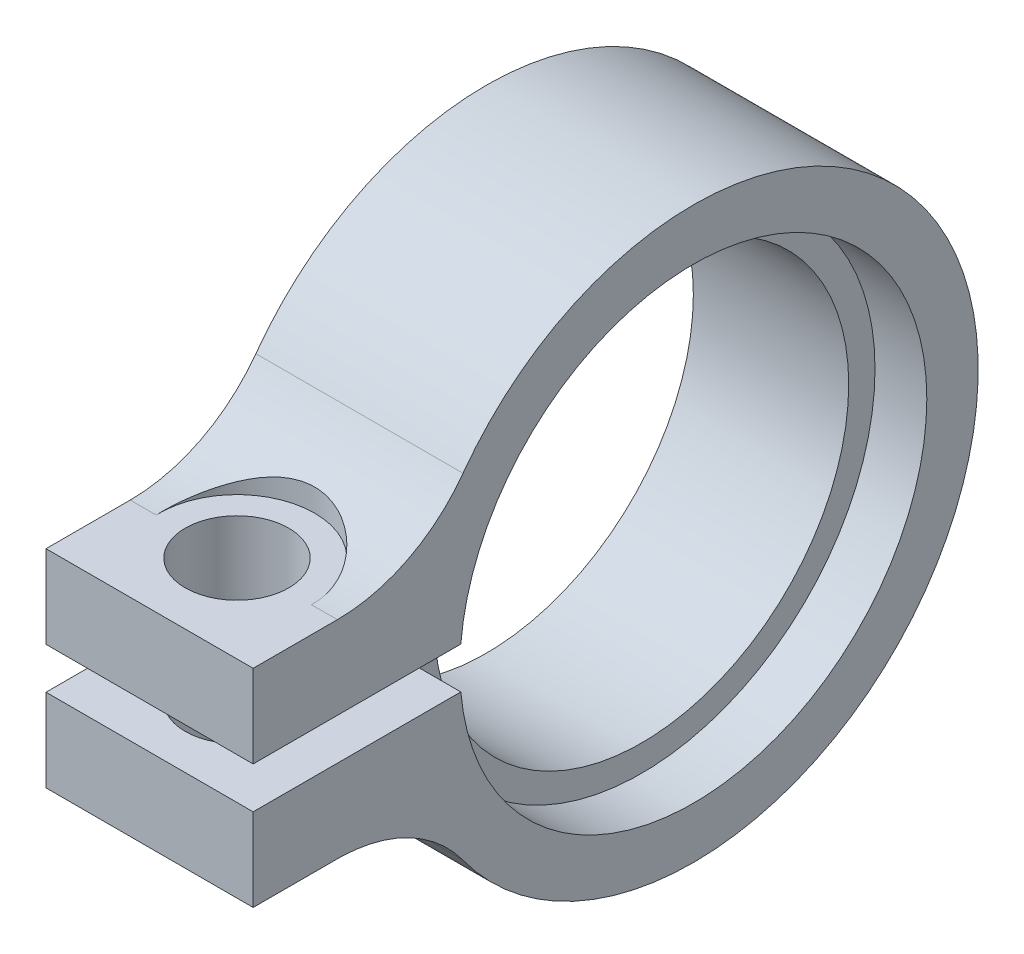
SolidWorks part; units mm, degrees
ref_plane "Front Plane" through (0, 0, 0) normal (0, 0, 1) x (1, 0, 0)
ref_plane "Top Plane" through (0, 0, 0) normal (0, 1, 0) x (1, 0, 0)
ref_plane "Right Plane" through (0, 0, 0) normal (1, 0, 0) x (0, 0, -1)
sketch "Sketch1" plane through (-50.8, 0, 0) normal (-1, 0, 0) x (0, 0, 1)
  line L0 (12.7, 187.45) -> (26.9875, 187.45) construction
  line L1 (12.6363, 186.18) -> (26.9875, 186.18)
  line L2 (12.6363, 188.72) -> (26.9875, 188.72)
  line L3 (26.9875, 188.72) -> (26.9875, 193.8)
  line L4 (26.9875, 193.8) -> (16.267, 193.8)
  line L5 (26.9875, 186.18) -> (26.9875, 181.1)
  line L6 (26.9875, 181.1) -> (16.267, 181.1)
  line L7 (12.7, 186.18) -> (26.9875, 186.18) construction
  line L8 (12.7, 188.72) -> (26.9875, 188.72) construction
  circle A0 centre (0, 187.45) radius 12.7 construction
  circle A1 centre (0, 187.45) radius 14.3129
  circle A2 centre (0, 187.45) radius 14.3129
  circle A3 centre (0, 187.45) radius 12.7
  circle A4 centre (0, 187.45) radius 17.4625
  point P18 (17.4625, 187.45)
  circle M5 centre (0, 187.45) radius 14.3129
  circle M6 centre (0, 187.45) radius 12.7
  dimension "D2" = 4.7625
  dimension "D5" = 9.525
  dimension "D6" = 5.08
  dimension "D1" = 0
  dimension "D3" = 1.27
  dimension "D4" = 1.27
extrude "Boss-Extrude1" add sketch "Sketch1" along normal blind 9.525 contours L2 L1 M6 M5 | L2 A4 L1 M5 | A4 L6 L5 L1 | A4 L2 L3 L4 region at (-50.8, 185.7756, 13.4464) region at (-50.8, 185.6864, 15.8364) region at (-50.8, 183.5916, 21.9758) region at (-50.8, 191.3084, 21.9758)
extrude "Boss-Extrude2" add sketch "Sketch1<4>" against normal up to surface (3.175 mm away) contours L2 A4 L1 M5 | A4 L2 L3 L4 | A4 L6 L5 L1 region at (-50.8, 185.6864, 15.8364) region at (-50.8, 183.5916, 21.9758) region at (-50.8, 191.3084, 21.9758)
sketch "Sketch1<4>" plane through (-50.8, 0, 0) normal (-1, 0, 0) x (0, 0, 1) same geometry as "Sketch1"
sketch "Sketch2" plane through (0, 193.8, 0) normal (0, 1, 0) x (1, 0, 0)
  line L0 (-60.325, -16.267) -> (-47.625, -26.9875) construction
  line L2 (-60.3908, -21.6273) -> (-57.1829, -27.1835)
  line L3 (-57.1829, -27.1835) -> (-50.7671, -27.1835)
  line L4 (-60.325, -26.9875) -> (-47.625, -26.9875)
  line L5 (-47.625, -26.9875) -> (-47.625, -16.267)
  line L6 (-47.625, -16.267) -> (-60.325, -16.267)
  line L7 (-60.325, -16.267) -> (-60.325, -26.9875)
  line L8 (-60.325, -26.9875) -> (-47.625, -26.9875) construction
  line L9 (-47.625, -26.9875) -> (-47.625, -16.267) construction
  line L10 (-47.625, -16.267) -> (-60.325, -16.267) construction
  line L11 (-60.325, -16.267) -> (-60.325, -26.9875) construction
  line L12 (-50.7671, -27.1835) -> (-47.5592, -21.6273)
  line L13 (-47.5592, -21.6273) -> (-50.7671, -16.071)
  line L14 (-50.7671, -16.071) -> (-57.1829, -16.071)
  line L15 (-57.1829, -16.071) -> (-60.3908, -21.6273)
  circle A0 centre (-53.975, -21.6273) radius 3.175
  circle A1 centre (-53.975, -21.6273) radius 4.7625
  circle A2 centre (-53.975, -21.6273) radius 5.5562 construction
  line M6 (-60.325, -26.9875) -> (-47.625, -26.9875)
  line M7 (-47.625, -26.9875) -> (-47.625, -16.267)
  line M8 (-47.625, -16.267) -> (-60.325, -16.267)
  line M9 (-60.325, -16.267) -> (-60.325, -26.9875)
  dimension "D2" = 6.35
  dimension "D3" = 9.525
  dimension "D4" = 11.1125
  dimension "D1" = 0
fillet "Fillet1" radius 9.525 2 edges at (-53.975, 181.1, 16.267) (-53.975, 193.8, 16.267)
extrude "Cut-Extrude1" cut sketch "Sketch2" along normal through all contours A1 A0 | A0 region at (-53.975, 193.8, 21.6273) region at (-58.6028, 193.8, 21.6273)
extrude "Cut-Extrude2" cut sketch "Sketch2<4>" against normal through all contours A0 region at (-53.975, 193.8, 21.6273)
sketch "Sketch2<4>" plane through (0, 193.8, 0) normal (0, 1, 0) x (1, 0, 0) same geometry as "Sketch2"
extrude "Cut-Extrude4" cut sketch "Sketch2<6>" against normal through all from surface contours L15 L2 L12 L13 A1 M8 M9 M6 M7 | A1 A0 | A0 region at (-60.1588, 193.8, 21.6273) region at (-53.975, 193.8, 21.6273) region at (-58.6028, 193.8, 21.6273) starting at face at (-53.975, 181.1, 24.0418)
sketch "Sketch2<6>" plane through (0, 193.8, 0) normal (0, 1, 0) x (1, 0, 0) same geometry as "Sketch2"
